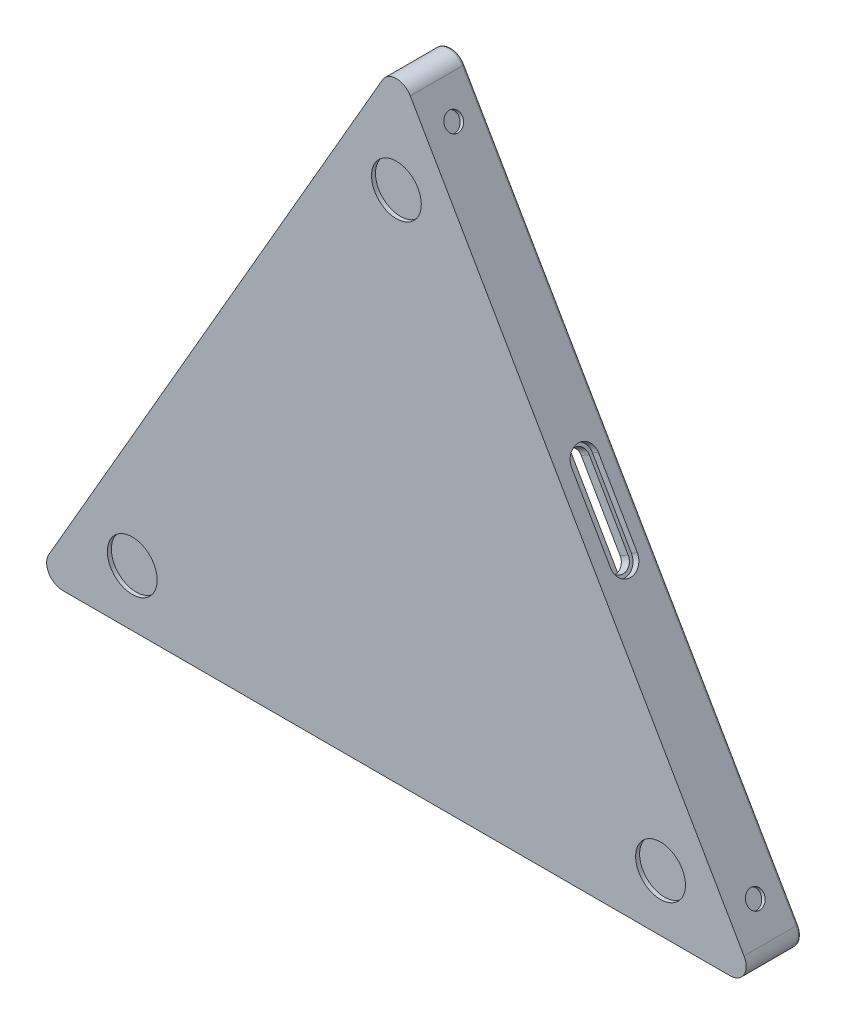
SolidWorks part; units mm, degrees
ref_plane "Plan de face" through (0, 0, 0) normal (0, 0, 1) x (1, 0, 0)
ref_plane "Plan de dessus" through (0, 0, 0) normal (0, 1, 0) x (1, 0, 0)
ref_plane "Plan de droite" through (0, 0, 0) normal (1, 0, 0) x (0, 0, -1)
sketch "Esquisse1" plane through (0, 0, 0) normal (0, 0, 1) x (1, 0, 0)
  line L0 (-169.7182, -51.3779) -> (-57.2182, 143.4778)
  line L1 (-57.2182, 143.4778) -> (55.2818, -51.3779)
  line L2 (55.2818, -51.3779) -> (-169.7182, -51.3779)
  line L3 (46.6215, -46.3779) -> (-161.058, -46.3779)
  line L4 (-161.058, -46.3779) -> (-57.2182, 133.4778)
  line L5 (-57.2182, 133.4778) -> (46.6215, -46.3779)
  dimension "D1" = 225
  dimension "D2" = 5
extrude "Boss.-Extru.1" add sketch "Esquisse1" along normal blind 15
sketch "Esquisse2" plane through (0, 0, 15) normal (0, 0, 1) x (1, 0, 0)
  line L0 (-57.2182, 143.4778) -> (-169.7182, -51.3779) construction
  line L1 (-169.7182, -51.3779) -> (55.2818, -51.3779) construction
  line L2 (55.2818, -51.3779) -> (-57.2182, 143.4778) construction
  line L3 (-57.2182, 143.4778) -> (-169.7182, -51.3779)
  line L4 (-169.7182, -51.3779) -> (55.2818, -51.3779)
  line L5 (55.2818, -51.3779) -> (-57.2182, 143.4778)
extrude "Boss.-Extru.2" add sketch "Esquisse2" along normal blind 2
sketch "Esquisse3" plane through (0, 0, 15) normal (0, 0, -1) x (-1, 0, 0)
  line L0 (53.949, 117.8154) -> (-28.5164, -25.019)
  line L1 (-46.6215, -46.3779) -> (57.2182, 133.4778) construction
  line L2 (53.949, 117.8154) -> (55.1614, 117.1154)
  line L3 (55.1614, 117.1154) -> (-27.304, -25.719)
  line L4 (-27.304, -25.719) -> (-28.5164, -25.019)
  line L5 (57.2182, 133.4778) -> (57.2182, -131.0717) construction
  line L6 (161.058, -46.3779) -> (-46.6215, -46.3779) construction
  line L7 (183.4656, -59.0638) -> (-91.5534, 99.7185) construction
  line L8 (-55.2818, -51.3779) -> (57.2182, 143.4778) construction
  line L25 (-46.6215, -46.3779) -> (181.6985, 85.4427) construction
  line L26 (57.2182, 143.4778) -> (169.7182, -51.3779) construction
  line L55 (149.0198, -35.5271) -> (147.8073, -36.2271)
  line L56 (149.0198, -35.5271) -> (66.5543, 107.3072)
  line L57 (65.3419, 106.6072) -> (66.5543, 107.3072)
  line L58 (147.8073, -36.2271) -> (65.3419, 106.6072)
  line L59 (-31.4228, -41.3779) -> (-31.4228, -39.9779)
  line L60 (-31.4228, -41.3779) -> (133.508, -41.3779)
  line L61 (133.508, -39.9779) -> (133.508, -41.3779)
  line L62 (-31.4228, -39.9779) -> (133.508, -39.9779)
  line L63 (57.2182, 133.4778) -> (161.058, -46.3779) construction
  line L64 (161.058, -46.3779) -> (-46.6215, -46.3779) construction
  dimension "D1" = 28
  dimension "D2" = 16
  dimension "D3" = 1.4
  dimension "D4" = 5
  dimension "D5" = 164.9309
  dimension "D6" = 1.4
  dimension "D7" = 5
  dimension "D8" = 5
  dimension "D9" = 5
  dimension "D10" = 1.4
extrude "Boss.-Extru.3" add sketch "Esquisse3" along normal blind 11
sketch "Esquisse4" plane through (19.214, 11.0932, 0) normal (0.866, 0.5, 0) x (0, 0, -1)
  line L0 (0, 40.3645) -> (-17, 40.3645) construction
  line L1 (-12.65, 52.4645) -> (-4.35, 28.2645) construction
  line L3 (-12.65, 52.4645) -> (-12.65, 28.2645)
  line L5 (-4.35, 52.4645) -> (-4.35, 28.2645)
  line L6 (-4.35, 52.4645) -> (-12.65, 28.2645) construction
  arc A0 (-4.35, 52.4645) -> (-12.65, 52.4645) centre (-8.5, 52.4645) ccw
  arc A1 (-12.65, 28.2645) -> (-4.35, 28.2645) centre (-8.5, 28.2645) ccw
  point P4 (-8.5, 40.3645)
  point P6 (-8.5, 40.3645)
  point P8 (-8.5, 56.6145)
  point P11 (-8.5, 24.1145)
  dimension "D1" = 8.3
  dimension "D2" = 32.5
extrude "Enlèv. mat.-Extru.1" cut sketch "Esquisse4" against normal blind 2.1
sketch "Esquisse5" plane through (17.3954, 10.0432, 0) normal (0.866, 0.5, 0) x (0, 0, -1)
  line L4 (-11.65, 52.4645) -> (-11.65, 28.2645)
  line L5 (-5.35, 28.2645) -> (-5.35, 52.4645)
  line L6 (-11.65, 52.4645) -> (-11.65, 28.2645)
  line L7 (-5.35, 28.2645) -> (-5.35, 52.4645)
  arc A4 (-11.65, 28.2645) -> (-5.35, 28.2645) centre (-8.5, 28.2645) ccw
  arc A5 (-5.35, 52.4645) -> (-11.65, 52.4645) centre (-8.5, 52.4645) ccw
  arc A6 (-11.65, 28.2645) -> (-5.35, 28.2645) centre (-8.5, 28.2645) ccw
  arc A7 (-5.35, 52.4645) -> (-11.65, 52.4645) centre (-8.5, 52.4645) ccw
  dimension "D1" = 1
extrude "Enlèv. mat.-Extru.2" cut sketch "Esquisse5" against normal up to next
fillet "Congé1" radius 5 6 edges at (-161.058, -46.3779, 7.5) (46.6215, -46.3779, 7.5) (-57.2182, 133.4778, 7.5) (-57.2182, 143.4778, 8.5) (-169.7182, -51.3779, 8.5) (55.2818, -51.3779, 8.5)
ref_plane "Plan1" through (-8.4268, -14.5957, 0) normal (0.5, 0.866, 0) x (0.866, -0.5, 0)
mirror "Symétrie1" about plane through (-8.4268, -14.5957, 0) normal (0.5, 0.866, 0) of "Enlèv. mat.-Extru.2", "Enlèv. mat.-Extru.1"
sketch "Esquisse6" plane through (0, 0, 17) normal (0, 0, 1) x (1, 0, 0)
  line L0 (-57.2182, 138.4778) -> (-57.2182, -78.2575) construction
  line L1 (-1.8061, -18.4182) -> (-15.0476, -10.7732) construction
  arc A0 (-52.8881, 135.9778) -> (-61.5484, 135.9778) centre (-57.2182, 133.4778) ccw construction
  circle A1 centre (-57.2182, 108.4778) radius 7.75
  circle A2 centre (-139.4073, -33.8779) radius 7.75
  circle A3 centre (24.9709, -33.8779) radius 7.75
  dimension "D1" = 15.5
  dimension "D2" = 30
extrude "Enlèv. mat.-Extru.3" cut sketch "Esquisse6" against normal blind 1.24
sketch "Esquisse7" plane through (0, -51.3779, 0) normal (0, -1, 0) x (1, 0, 0)
  line L0 (-161.058, 8.5) -> (46.6215, 8.5) construction
  line L1 (-161.058, 17) -> (-161.058, 0) construction
  line L2 (46.6215, 0) -> (46.6215, 17) construction
  line L3 (-57.2182, 17) -> (-57.2182, 0) construction
  line L4 (-161.058, 17) -> (46.6215, 17) construction
  line L5 (-161.058, 0) -> (46.6215, 0) construction
  circle A0 centre (36.6215, 8.5) radius 2.75
  circle A1 centre (-151.058, 8.5) radius 2.75
  dimension "D1" = 5.5
  dimension "D2" = 10
  dimension "D3" = 10
extrude "Enlèv. mat.-Extru.4" cut sketch "Esquisse7" against normal blind 1.24
mirror "Symétrie2" about plane through (-8.4268, -14.5957, 0) normal (0.5, 0.866, 0) of "Enlèv. mat.-Extru.4"
ref_plane "Plan2" through (-20.1823, 34.9567, 0) normal (0.5, -0.866, 0) x (-0.866, -0.5, 0)
mirror "Symétrie3" about plane through (-20.1823, 34.9567, 0) normal (0.5, -0.866, 0) of "Enlèv. mat.-Extru.4"
fillet "Congé2" radius 5 3 edges at (-12.7163, 46.3982, 15) (-51.0426, -41.3779, 15) (-107.787, 35.8901, 15)
sketch "Esquisse9" plane through (0, 0, 0) normal (0, 0, -1) x (-1, 0, 0)
  line L6 (164.0891, -44.6279) -> (60.2493, 135.2278)
  line L7 (54.1871, 135.2278) -> (-49.6526, -44.6279)
  line L8 (-46.6215, -49.8779) -> (161.058, -49.8779)
  line L9 (164.0891, -44.6279) -> (60.2493, 135.2278)
  line L10 (54.1871, 135.2278) -> (-49.6526, -44.6279)
  line L11 (-46.6215, -49.8779) -> (161.058, -49.8779)
  arc A6 (60.2493, 135.2278) -> (54.1871, 135.2278) centre (57.2182, 133.4778) ccw
  arc A7 (-49.6526, -44.6279) -> (-46.6215, -49.8779) centre (-46.6215, -46.3779) ccw
  arc A8 (161.058, -49.8779) -> (164.0891, -44.6279) centre (161.058, -46.3779) ccw
  arc A9 (60.2493, 135.2278) -> (54.1871, 135.2278) centre (57.2182, 133.4778) ccw
  arc A10 (-49.6526, -44.6279) -> (-46.6215, -49.8779) centre (-46.6215, -46.3779) ccw
  arc A11 (161.058, -49.8779) -> (164.0891, -44.6279) centre (161.058, -46.3779) ccw
  dimension "D1" = 1.5
extrude "Enlèv. mat.-Extru.6" cut sketch "Esquisse9" against normal blind 2
sketch "Esquisse8" plane through (0, 0, 0) normal (0, 0, -1) x (-1, 0, 0)
  line L0 (15.5716, -10.4707) -> (1.2821, -18.7207) construction
  line L2 (-42.2914, -43.8779) -> (-50.9516, -48.8779) construction
  line L3 (13.9902, 38.5317) -> (26.3743, 31.3817) construction
  circle A0 centre (-45.9149, -45.9699) radius 2.75
  arc A3 (-37.9613, -46.3779) -> (-42.2914, -38.8779) centre (-37.9613, -41.3779) ccw construction
  arc A4 (-50.9516, -43.8779) -> (-46.6215, -51.3779) centre (-46.6215, -46.3779) ccw construction
  circle A5 centre (57.2182, 132.6619) radius 2.75
  circle A6 centre (160.3514, -45.9699) radius 2.75
  dimension "D1" = 5.5
extrude "Enlèv. mat.-Extru.5" cut sketch "Esquisse8" against normal blind 4.1
sketch3d "Esquisse3D1"
  line L6 (-164.0891, -44.6279, 2) -> (-60.2493, 135.2278, 2)
  line L7 (-54.1871, 135.2278, 2) -> (49.6526, -44.6279, 2)
  line L8 (46.6215, -49.8779, 2) -> (-161.058, -49.8779, 2)
  line L9 (-164.0891, -44.6279, 2) -> (-60.2493, 135.2278, 2)
  line L10 (-54.1871, 135.2278, 2) -> (49.6526, -44.6279, 2)
  line L11 (46.6215, -49.8779, 2) -> (-161.058, -49.8779, 2)
  circle A0 centre (45.9149, -45.9699, 2) radius 2.75 construction
  circle A1 centre (-57.2182, 132.6619, 2) radius 2.75 construction
  circle A2 centre (45.9149, -45.9699, 2) radius 2.75
  circle A3 centre (-57.2182, 132.6619, 2) radius 2.75
  circle A6 centre (-160.3514, -45.9699, 2) radius 2.75 construction
  circle A7 centre (-160.3514, -45.9699, 2) radius 2.75
  arc A9 (-161.058, -49.8779, 2) -> (-164.0891, -44.6279, 2) centre (-161.058, -46.3779, 2) ccw
  arc A10 (-60.2493, 135.2278, 2) -> (-54.1871, 135.2278, 2) centre (-57.2182, 133.4778, 2) ccw
  arc A11 (49.6526, -44.6279, 2) -> (46.6215, -49.8779, 2) centre (46.6215, -46.3779, 2) ccw
  arc A12 (-161.058, -49.8779, 2) -> (-164.0891, -44.6279, 2) centre (-161.058, -46.3779, 2) ccw
  arc A13 (-60.2493, 135.2278, 2) -> (-54.1871, 135.2278, 2) centre (-57.2182, 133.4778, 2) ccw
  arc A14 (49.6526, -44.6279, 2) -> (46.6215, -49.8779, 2) centre (46.6215, -46.3779, 2) ccw
  point P2 (45.9149, -45.9699, -0.75)
  point P5 (-57.2182, 132.6619, -0.75)
  point P7 (45.9149, -45.9699, -0.75)
  point P9 (-57.2182, 132.6619, -0.75)
  point P16 (-160.3514, -45.9699, -0.75)
  point P17 (-161.058, -46.3779, -1.5)
  point P22 (-160.3514, -45.9699, -0.75)
  point P23 (-57.2182, 133.4778, -1.5)
  point P27 (46.6215, -46.3779, -1.5)
  point P28 (-161.058, -46.3779, -1.5)
  point P29 (-57.2182, 133.4778, -1.5)
  point P30 (46.6215, -46.3779, -1.5)
  dimension "D1" = 0
fillet "Congé3" 2 edges at (-57.2182, -51.3779, 0) (-57.2182, -49.8779, 0) type full round first side face at (39.3715, -51.3779, 8.5) second side face at (-57.2182, -49.8779, 1) middle face at (-57.2182, 13.574, 0)
